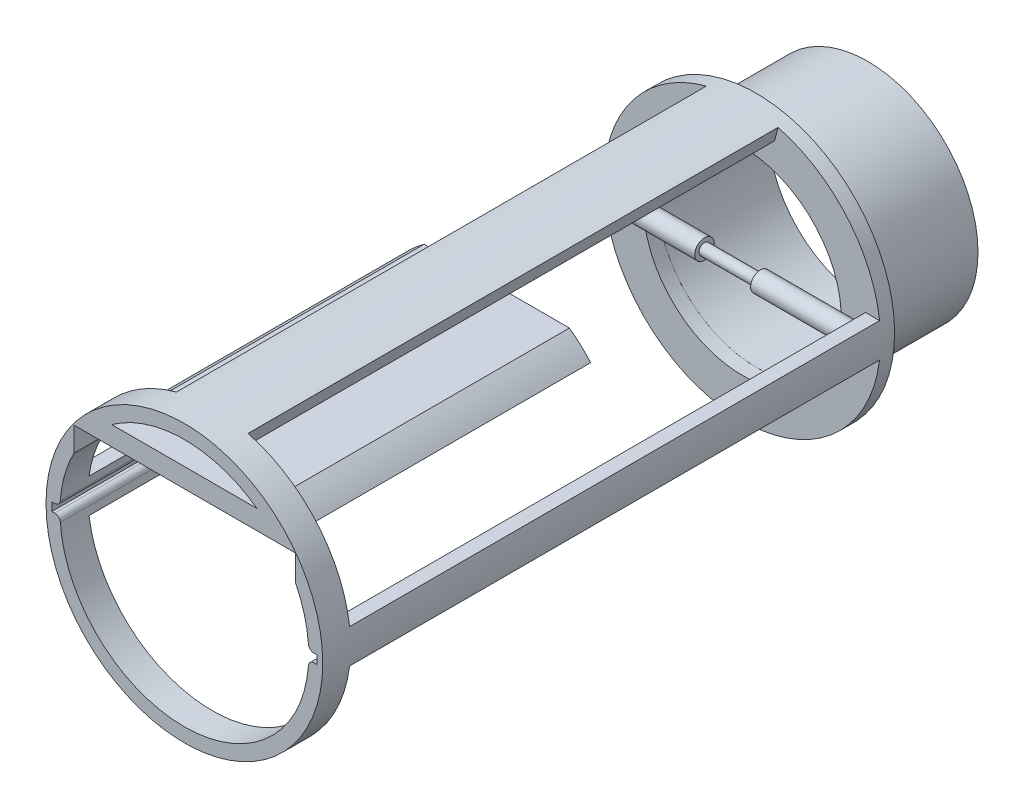
SolidWorks part; units mm, degrees
ref_plane "Front Plane" through (0, 0, 0) normal (0, 0, 1) x (1, 0, 0)
ref_plane "Top Plane" through (0, 0, 0) normal (0, 1, 0) x (1, 0, 0)
ref_plane "Right Plane" through (0, 0, 0) normal (1, 0, 0) x (0, 0, -1)
sketch "Sketch1" plane through (0, 0, 0) normal (0, 0, 1) x (1, 0, 0)
  circle A0 centre (0, 0) radius 19.75
  circle A1 centre (0, 0) radius 17.75
extrude "Boss-Extrude1" add sketch "Sketch1" along normal blind 20
sketch "Sketch2" plane through (0, 0, 20) normal (0, 0, 1) x (1, 0, 0)
  circle A0 centre (0, 0) radius 24.8
  circle A2 centre (0, 0) radius 17.75 construction
  circle A3 centre (0, 0) radius 17.75
extrude "Boss-Extrude2" add sketch "Sketch2" along normal blind 2.5 separate body
sketch "Sketch3" plane through (0, 0, 22.5) normal (0, 0, 1) x (1, 0, 0)
  circle A0 centre (0, 0) radius 24.8 construction
  circle A1 centre (0, 0) radius 24.8
  circle A2 centre (0, 0) radius 22.3
extrude "Boss-Extrude3" add sketch "Sketch3" along normal blind 100
sketch "Sketch4" plane through (0, 0, 122.5) normal (0, 0, 1) x (1, 0, 0)
  line L1 (-23.75, 0.75) -> (23.75, 0.75)
  line L2 (-23.75, 0.75) -> (-23.75, -0.75)
  line L3 (-23.75, -0.75) -> (23.75, -0.75)
  line L4 (23.75, 0.75) -> (23.75, -0.75)
  point P6 (0, 0.75)
  point P7 (23.75, 0)
extrude "Cut-Extrude1" cut sketch "Sketch4" against normal blind 100
sketch "Sketch6" plane through (0, 0, 122.5) normal (0, 0, 1) x (1, 0, 0)
  line L0 (-24.611, 3.0561) -> (-22.0896, 3.0561)
  line L2 (24.611, -3.0561) -> (22.0896, -3.0561)
  line L3 (22.0896, 3.0561) -> (24.611, 3.0561)
  line L4 (-22.0896, -3.0561) -> (-24.611, -3.0561)
  arc A0 (22.2874, 0.75) -> (-22.2874, 0.75) centre (0, 0) ccw construction
  arc A1 (22.0896, 3.0561) -> (-22.0896, 3.0561) centre (0, 0) ccw
  arc A2 (-22.2874, -0.75) -> (22.2874, -0.75) centre (0, 0) ccw construction
  arc A3 (-22.0896, -3.0561) -> (22.0896, -3.0561) centre (0, 0) ccw
  circle A4 centre (0, 0) radius 24.8 construction
  arc A5 (-24.611, -3.0561) -> (24.611, -3.0561) centre (0, 0) ccw
  arc A6 (24.611, 3.0561) -> (-24.611, 3.0561) centre (0, 0) ccw
extrude "Cut-Extrude3" cut sketch "Sketch6" against normal blind 95 from offset 5 offset against normal yes
sketch "Sketch7" plane through (-23.75, 0, 0) normal (1, 0, 0) x (0, 0, -1)
  circle A0 centre (-24.0194, 0) radius 1.75
extrude "Boss-Extrude4" add sketch "Sketch7" along normal blind 18.5
sketch "Sketch9" plane through (-5.25, 0, 0) normal (1, 0, 0) x (0, 0, -1)
  circle A0 centre (-24.0194, 0) radius 1
extrude "Boss-Extrude5" add sketch "Sketch9" along normal blind 10
sketch "Sketch10" plane through (4.75, 0, 0) normal (1, 0, 0) x (0, 0, -1)
  circle A0 centre (-24.0194, 0) radius 1.75 construction
  circle A1 centre (-24.0194, 0) radius 1.75
extrude "Boss-Extrude6" add sketch "Sketch10" along normal up to surface (19 mm away) up to face at (23.75, 0, 72.5)
sketch "Sketch12" plane through (0, 0, 122.5) normal (0, 0, 1) x (1, 0, 0)
  line L0 (-19.7995, 14.6391) -> (19.9505, 14.6391)
  line L1 (-19.7995, 14.6391) -> (-19.7995, 4.3891)
  line L2 (19.9505, 14.6391) -> (19.9505, 4.3891)
  line L3 (-19.7995, 4.3891) -> (19.9505, 4.3891)
  line L4 (-19.7995, 4.3891) -> (-21.8638, 4.3891)
  line L5 (-21.8638, 4.3891) -> (21.8638, 4.3891)
  arc A0 (22.2874, 0.75) -> (-22.2874, 0.75) centre (0, 0) ccw construction
  arc A1 (22.2874, 0.75) -> (19.9505, 9.9633) centre (0, 0) ccw
  circle A2 centre (0, 0) radius 24.8 construction
  circle A3 centre (0, 0) radius 24.8
  arc A4 (-19.7995, 10.2601) -> (-22.2874, 0.75) centre (0, 0) ccw
  arc A5 (16.8223, 14.6391) -> (-16.8223, 14.6391) centre (0, 0) ccw
  arc M7 (-22.2874, 0.75) -> (22.2874, 0.75) centre (0, 0) cw
extrude "Cut-Extrude4" cut sketch "Sketch12" against normal blind 10 contours L1 L3 L2 L0 M7 | L0 L1 M7 | L2 L0 M7 region at (-18.8486, 13.2443, 122.5) region at (0.0435, 9.3965, 122.5) region at (18.9543, 13.1549, 122.5)
sketch "Sketch13" plane through (0, 0, 122.5) normal (0, 0, 1) x (1, 0, 0)
  line L0 (-19.7995, 14.6391) -> (19.9505, 14.6391)
  line L1 (16.9456, 18.1076) -> (-16.9456, 18.1076)
  line L2 (19.9505, 14.6391) -> (20.0184, 14.6391)
  line L3 (-19.7995, 14.6391) -> (-20.0184, 14.6391)
  line L5 (5.7717, 21.5401) -> (6.4187, 23.955)
  line L7 (-5.7717, 21.5401) -> (-6.4187, 23.955)
  arc A0 (16.8223, 14.6391) -> (-16.8223, 14.6391) centre (0, 0) ccw construction
  circle A1 centre (0, 0) radius 24.8 construction
  arc A3 (16.8223, 14.6391) -> (13.0155, 18.1076) centre (0, 0) ccw
  arc A4 (20.0184, 14.6391) -> (16.9456, 18.1076) centre (0, 0) ccw
  arc A5 (-13.0155, 18.1076) -> (-16.8223, 14.6391) centre (0, 0) ccw
  arc A6 (5.7717, 21.5401) -> (-5.7717, 21.5401) centre (0, 0) ccw
  arc A7 (-16.9456, 18.1076) -> (-20.0184, 14.6391) centre (0, 0) ccw
  arc A8 (6.4187, 23.955) -> (-6.4187, 23.955) centre (0, 0) ccw
  arc M17 (-16.8223, 14.6391) -> (16.8223, 14.6391) centre (0, 0) cw
extrude "Boss-Extrude7" add sketch "Sketch13" against normal blind 56 contours L1 L0 M17 region at (0, 16.3007, 122.5)
sketch "Sketch15" plane through (0, 0, 122.5) normal (0, 0, 1) x (1, 0, 0)
  line L0 (5.7717, 21.5401) -> (6.4187, 23.955)
  line L2 (-6.4187, 23.955) -> (-5.7717, 21.5401)
  arc A0 (13.0155, 18.1076) -> (-13.0155, 18.1076) centre (0, 0) ccw construction
  circle A1 centre (0, 0) radius 24.8
  arc A2 (6.4187, 23.955) -> (-6.4187, 23.955) centre (0, 0) ccw
  arc A3 (5.7717, 21.5401) -> (-5.7717, 21.5401) centre (0, 0) ccw
  dimension "D1" = 0
extrude "Boss-Extrude8" add sketch "Sketch15" against normal up to surface (100 mm away) up to face at (0, 6.791, 22.5)
fillet "Fillet1" radius 1 4 edges at (22.2874, -0.75, 74.0502) (22.2874, 0.75, 74.0502) (-22.2874, 0.75, 74.0502) (-22.2874, -0.75, 74.0502)
